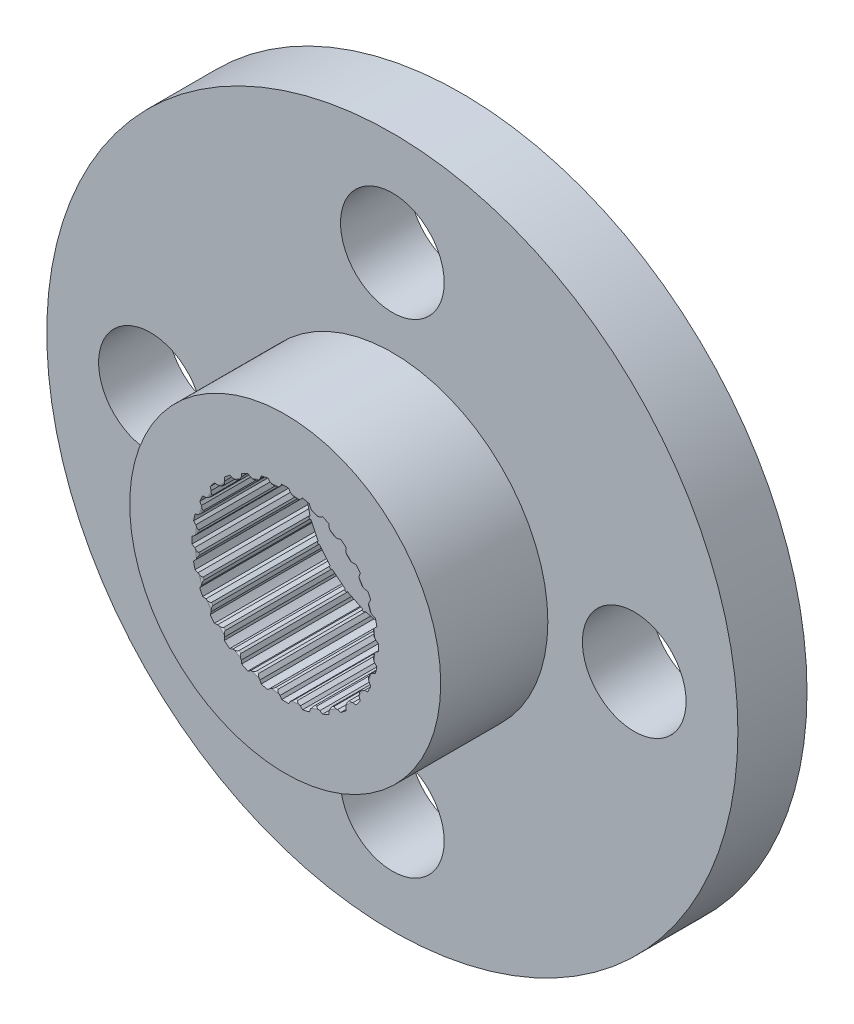
SolidWorks part; units mm, degrees
material "Beryllium"
ref_plane "Alzado" through (0, 0, 0) normal (0, 0, 1) x (1, 0, 0)
ref_plane "Planta" through (0, 0, 0) normal (0, 1, 0) x (1, 0, 0)
ref_plane "Vista lateral" through (0, 0, 0) normal (1, 0, 0) x (0, 0, -1)
sketch "Croquis1" plane through (0, 0, 0) normal (0, 0, 1) x (1, 0, 0)
  circle A0 centre (0, 0) radius 7 construction
  circle A1 centre (0, 0) radius 10
  circle A2 centre (-7, 0) radius 1.5
  circle A3 centre (0, 7) radius 1.5
  circle A4 centre (0, -7) radius 1.5
  circle A5 centre (7, 0) radius 1.5
  circle A6 centre (0, 0) radius 1.5
  dimension "D1" = 14
  dimension "D2" = 20
  dimension "D3" = 3
extrude "Saliente-Extruir1" add sketch "Croquis1" along normal blind 2
sketch "Croquis3" plane through (0, 0, 2) normal (0, 0, 1) x (1, 0, 0)
  line L0 (0, 0) -> (0, 4.1004) construction
  circle A0 centre (0, 0) radius 4.5
  circle A1 centre (0, 0) radius 2.55
  dimension "D1" = 9
  dimension "D2" = 5.1
extrude "Saliente-Extruir3" add sketch "Croquis3" along normal blind 3.1
sketch "Croquis4" plane through (0, 0, 5.1) normal (0, 0, 1) x (1, 0, 0)
  line L0 (0, 0) -> (0, 3.2695) construction
  line L1 (0.246, 2.4975) -> (-0.246, 2.4975)
  line L2 (-0.246, 2.4975) -> (-0.25, 2.5377)
  line L3 (-0.25, 2.5377) -> (-0.15, 2.62)
  line L4 (-0.15, 2.62) -> (-0.1, 2.6981)
  line L5 (0.246, 2.4975) -> (0.25, 2.5377)
  line L6 (0.25, 2.5377) -> (0.15, 2.62)
  line L7 (0.15, 2.62) -> (0.1, 2.6981)
  circle A0 centre (0, 0) radius 2.55
  circle A1 centre (0, 0) radius 2.7
  point P13 (0, 2.4975)
  point P15 (0, 2.4975)
  circle M7 centre (0, 0) radius 2.55
  dimension "D1" = 5.1
  dimension "D2" = 5.4
  dimension "D7" = 2.4975
  dimension "D3" = 0.25
  dimension "D4" = 0.15
  dimension "D5" = 0.1
  dimension "D6" = 2.62
extrude "Cortar-Extruir2" cut sketch "Croquis4" against normal blind 3.4 contours L0 A0 L6 L7 A1 | L0 A1 L4 L3 M7 | L0 L1 L5 A0 | L1 L0 L2 M7 region at (-0.1189, 2.5219, 5.1) region at (0.1189, 2.5219, 5.1) region at (-0.0869, 2.6114, 5.1) region at (0.0869, 2.6114, 5.1)
fillet "Redondeo1" radius 0.05 1 edges at (0, -2.55, 5.1)
pattern_circular "MatrizC1" count 28 over 360 about axis through (0, 0, 5.1) along (0, 0, -1) of "Cortar-Extruir2"
